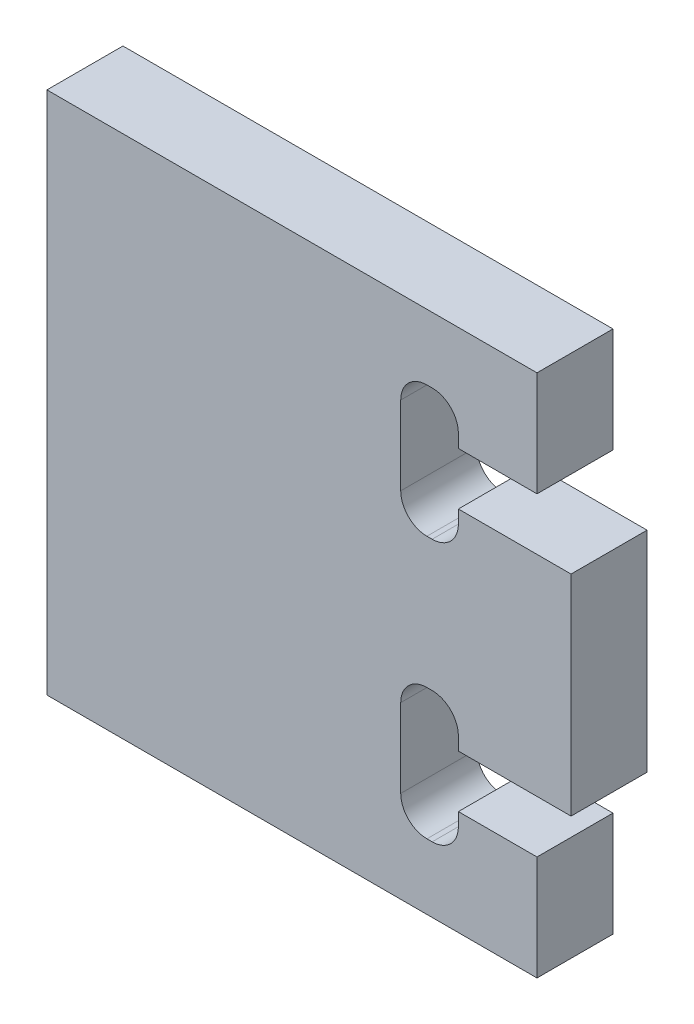
SolidWorks part; units mm, degrees
ref_plane "Front Plane" through (0, 0, 0) normal (0, 0, 1) x (1, 0, 0)
ref_plane "Top Plane" through (0, 0, 0) normal (0, 1, 0) x (1, 0, 0)
ref_plane "Right Plane" through (0, 0, 0) normal (1, 0, 0) x (0, 0, -1)
sketch "Sketch1" plane through (0, 0, 0) normal (0, 0, 1) x (1, 0, 0)
  line L0 (-39.5, 0) -> (39.5, 0) construction
  line L1 (-39.5, 10) -> (39.5, 10)
  line L2 (-39.5, 10) -> (-39.5, -10)
  line L3 (-39.5, -10) -> (39.5, -10)
  line L4 (39.5, 10) -> (39.5, -10)
  line L5 (-39.5, 10) -> (39.5, -10) construction
  line L6 (-39.5, -10) -> (39.5, 10) construction
  line L7 (0, 10) -> (0, -10) construction
  line L9 (-40.8, -4) -> (-39.5, -4)
  line L10 (-40.8, -4) -> (-40.8, 4)
  line L11 (-40.8, 4) -> (-39.5, 4)
  line L12 (-39.5, -4) -> (-39.5, 4)
  line L13 (-40.8, -4) -> (-39.5, 4) construction
  line L14 (-40.8, 4) -> (-39.5, -4) construction
  line L16 (40.8, 4) -> (39.5, 4)
  line L17 (40.8, -4) -> (40.8, 4)
  line L18 (40.8, -4) -> (39.5, -4)
  line L19 (-39.5, 5) -> (39.5, 5) construction
  line L20 (-35.4, 7.5) -> (-35.4, 2.5) construction
  line L21 (-36.5, 4) -> (-39.5, 4)
  line L22 (-36.5, 4) -> (-36.5, 6)
  line L23 (-36.5, 6) -> (-39.5, 6)
  line L24 (-39.5, 4) -> (-39.5, 6)
  line L25 (-36.5, 4) -> (-39.5, 6) construction
  line L26 (-36.5, 6) -> (-39.5, 4) construction
  line L27 (-34.3, 7.5) -> (-36.5, 7.5)
  line L28 (-34.3, 7.5) -> (-34.3, 2.5)
  line L29 (-34.3, 2.5) -> (-36.5, 2.5)
  line L30 (-36.5, 7.5) -> (-36.5, 2.5)
  line L31 (-34.3, 7.5) -> (-36.5, 2.5) construction
  line L32 (-34.3, 2.5) -> (-36.5, 7.5) construction
  line L33 (-34.3, -7.5) -> (-36.5, -7.5)
  line L34 (-34.3, -7.5) -> (-34.3, -2.5)
  line L35 (-34.3, -2.5) -> (-36.5, -2.5)
  line L36 (-36.5, -7.5) -> (-36.5, -2.5)
  line L37 (-36.5, -4) -> (-39.5, -4)
  line L38 (-36.5, -6) -> (-39.5, -6)
  line L39 (36.5, 4) -> (39.5, 4)
  line L40 (36.5, 6) -> (39.5, 6)
  line L41 (36.5, 7.5) -> (36.5, 2.5)
  line L42 (34.3, 7.5) -> (36.5, 7.5)
  line L43 (34.3, 7.5) -> (34.3, 2.5)
  line L44 (34.3, 2.5) -> (36.5, 2.5)
  line L45 (34.3, -2.5) -> (36.5, -2.5)
  line L46 (34.3, -7.5) -> (34.3, -2.5)
  line L47 (34.3, -7.5) -> (36.5, -7.5)
  line L48 (36.5, -7.5) -> (36.5, -2.5)
  line L49 (36.5, -6) -> (39.5, -6)
  line L50 (36.5, -4) -> (39.5, -4)
  point P0 (0, 0)
  point P10 (-40.15, 0)
  point P15 (-38, 5)
  point P35 (-35.4, 5)
  dimension "D1" = 79
  dimension "D2" = 20
  dimension "D4" = 1.3
  dimension "D7" = 5
  dimension "D8" = 2
  dimension "D9" = 3
  dimension "D10" = 2.2
  dimension "D11" = 5
extrude "Base shape" add sketch "Sketch1" along normal blind 2.9 contours L4 L1 L2 L3 | L9 L2 L11 L10 | L16 L4 L18 L17 region at (0, 0, 0) region at (-40.15, 0, 0) region at (40.15, 0, 0)
sketch "Sketch2" plane through (0, 0, 2.9) normal (0, 0, 1) x (1, 0, 0)
  circle A0 centre (0, 0) radius 5
  dimension "D1" = 10
extrude "Forward cut (temp)" cut sketch "Sketch2" against normal blind 1
fillet "Fillet1" radius 1 16 edges at (36.5, -7.5, 1.45) (36.5, 2.5, 1.45) (34.3, 2.5, 1.45) (34.3, -7.5, 1.45) (36.5, -2.5, 1.45) (36.5, 7.5, 1.45) (34.3, -2.5, 1.45) (34.3, 7.5, 1.45) (-36.5, -2.5, 1.45) (-34.3, -2.5, 1.45) (-34.3, -7.5, 1.45) (-36.5, -7.5, 1.45) (-36.5, 2.5, 1.45) (-34.3, 2.5, 1.45) (-34.3, 7.5, 1.45) (-36.5, 7.5, 1.45)
sketch "Sketch3" plane through (-40.8, 0, 0) normal (-1, 0, 0) x (0, 0, 1)
  line L0 (0, 6) -> (2.9, 4) construction
  line L1 (0, 6) -> (2.9, 6)
  line L2 (0, 6) -> (0, 4)
  line L3 (0, 4) -> (2.9, 4)
  line L4 (2.9, 6) -> (2.9, 4)
  line L5 (0, -4) -> (2.9, -6) construction
  line L6 (0, -4) -> (2.9, -4)
  line L7 (0, -4) -> (0, -6)
  line L8 (0, -6) -> (2.9, -6)
  line L9 (2.9, -4) -> (2.9, -6)
  point P6 (1.45, 5)
  point P13 (1.45, -5)
ref_axis "Tap axis top" through (-53.7846, 5, 1.45) along (1, 0, 0)
ref_axis "Tap axis bottom" through (-54.2844, -5, 1.45) along (1, 0, 0)
sketch "Sketch4" plane through (0, 0, 2.9) normal (0, 0, 1) x (1, 0, 0)
  line L0 (-39.5, 10) -> (39.5, 10) construction
  line L1 (20.8, 10) -> (-40.8, 10)
  line L2 (20.8, 10) -> (20.8, -10)
  line L3 (20.8, -10) -> (-40.8, -10)
  line L4 (-40.8, 10) -> (-40.8, -10)
  line L5 (-39.5, -10) -> (39.5, -10) construction
  line L7 (-40.8, -4) -> (-40.8, 4) construction
  line L8 (40.8, -4) -> (40.8, 4) construction
  dimension "D1" = 20
extrude "Cut-Extrude1" cut sketch "Sketch4" against normal up to next
